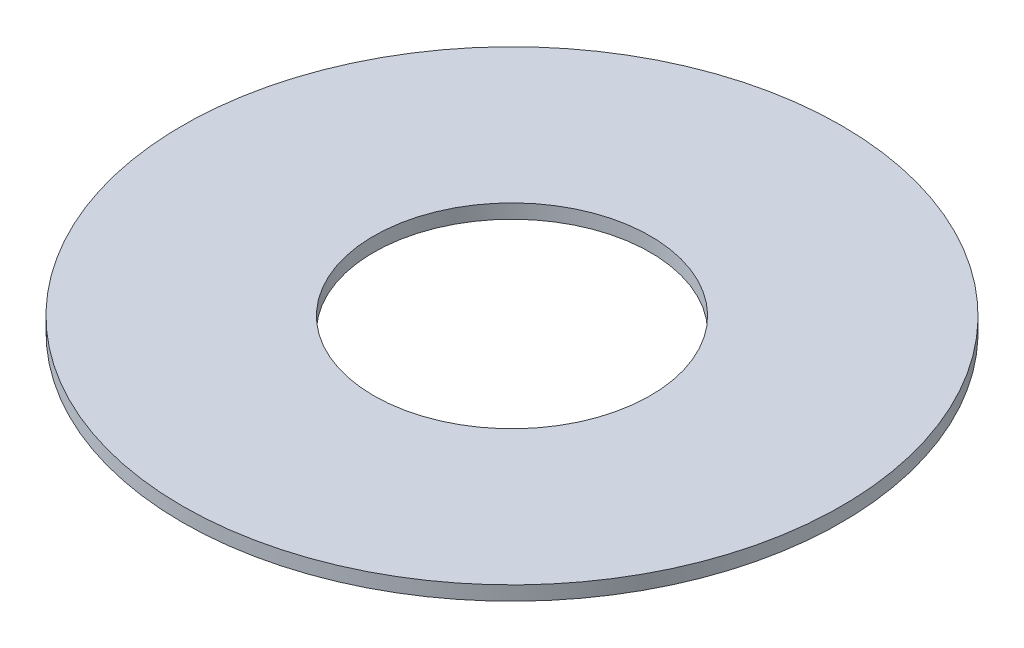
SolidWorks part; units mm, degrees
material "PTFE (general)"
ref_plane "Front Plane" through (0, 0, 0) normal (0, 0, 1) x (1, 0, 0)
ref_plane "Top Plane" through (0, 0, 0) normal (0, 1, 0) x (1, 0, 0)
ref_plane "Right Plane" through (0, 0, 0) normal (1, 0, 0) x (0, 0, -1)
sketch "Sketch1" plane through (0, 0, 0) normal (0, 1, 0) x (1, 0, 0)
  circle A0 centre (0, 0) radius 46.53
  circle A1 centre (0, 0) radius 19.53
  dimension "D1" = 39.06
  dimension "D2" = 93.06
extrude "Boss-Extrude1" add sketch "Sketch1" along normal blind 2
